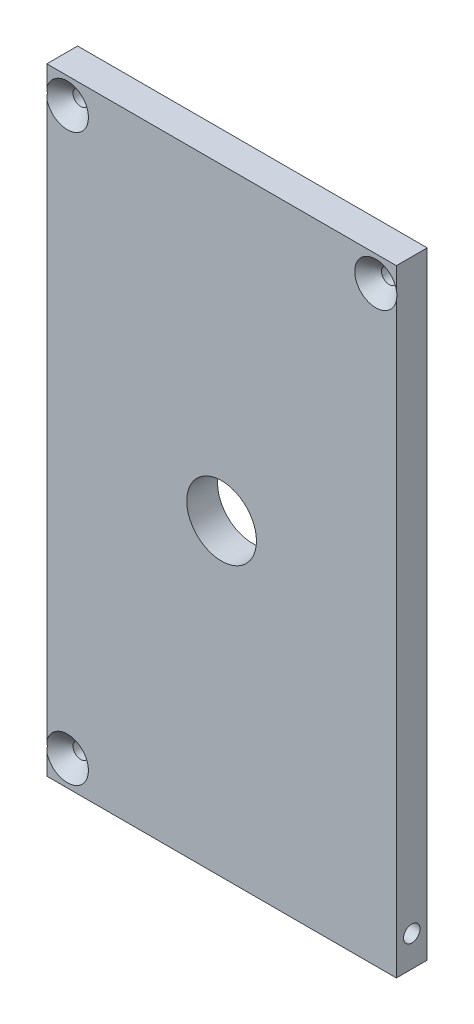
SolidWorks part; units mm, degrees
ref_plane "Front Plane" through (0, 0, 0) normal (0, 0, 1) x (1, 0, 0)
ref_plane "Top Plane" through (0, 0, 0) normal (0, 1, 0) x (1, 0, 0)
ref_plane "Right Plane" through (0, 0, 0) normal (1, 0, 0) x (0, 0, -1)
sketch "Sketch1" plane through (0, 0, 0) normal (0, 0, 1) x (1, 0, 0)
  line L0 (0, 0) -> (-37.4833, 0) construction
  line L1 (-17, -30) -> (17, -30)
  line L2 (-17, -30) -> (-17, 30)
  line L3 (-17, 30) -> (17, 30)
  line L4 (17, -30) -> (17, 30)
  line L5 (-17, -30) -> (17, 30) construction
  line L6 (-17, 30) -> (17, -30) construction
  line L7 (0, 0) -> (0, 18.7389) construction
  circle A0 centre (0, 0) radius 3.39
  circle A1 centre (-15, -27.5) radius 0.75
  circle A2 centre (-15, 27.5) radius 0.75
  circle A3 centre (15, 27.5) radius 0.75
  point P0 (0, 0)
  dimension "D3" = 6.78
  dimension "D4" = 1.5
  dimension "D1" = 60
  dimension "D2" = 34
  dimension "D5" = 2
  dimension "D6" = 2.5
extrude "Boss-Extrude1" add sketch "Sketch1" along normal blind 3
chamfer "Chamfer1" distance 1.3 angle 45 3 edges at (-14.25, -27.5, 3) (15.75, 27.5, 3) (-15.75, 27.5, 3)
sketch "Sketch2" plane through (17, 0, 0) normal (1, 0, 0) x (0, 0, -1)
  line L0 (-3, -30) -> (0, -30) construction
  line L1 (0, -30) -> (0, 30) construction
  circle A0 centre (-1.5, -27) radius 0.8
  dimension "D3" = 1.6
  dimension "D1" = 3
  dimension "D2" = 1.5
extrude "Cut-Extrude1" cut sketch "Sketch2" against normal blind 3
